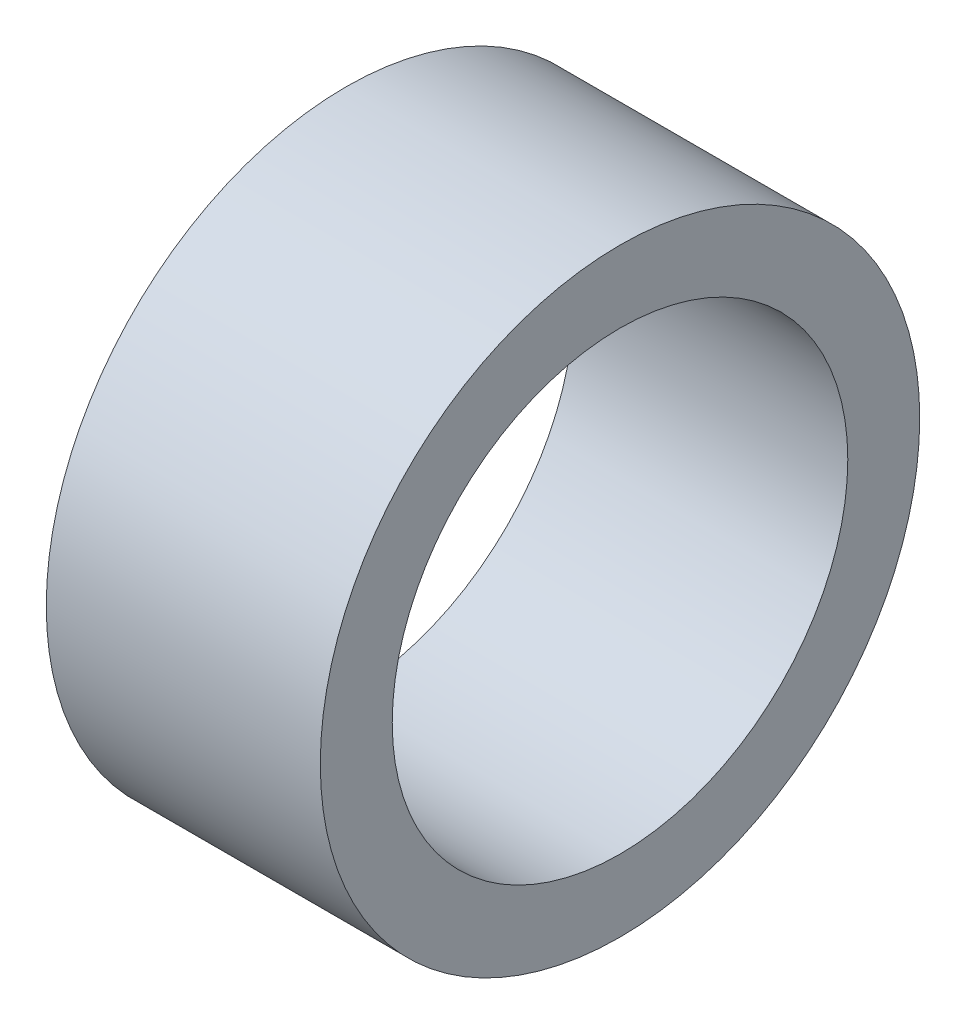
SolidWorks part; units mm, degrees
material "Nylon 6/10"
ref_plane "Front Plane" through (0, 0, 0) normal (0, 0, 1) x (1, 0, 0)
ref_plane "Top Plane" through (0, 0, 0) normal (0, 1, 0) x (1, 0, 0)
ref_plane "Right Plane" through (0, 0, 0) normal (1, 0, 0) x (0, 0, -1)
sketch "Sketch1" plane through (0, 0, 0) normal (0, 0, 1) x (1, 0, 0)
  line L0 (31.75, -13.8602) -> (31.75, 12.314) construction
  line L1 (31.75, 5.5563) -> (36.83, 5.5563)
  line L2 (31.75, 5.5563) -> (31.75, 4.2227)
  line L3 (31.75, 4.2227) -> (36.83, 4.2227)
  line L4 (36.83, 5.5563) -> (36.83, 4.2227)
  line L5 (0, 0) -> (42.6651, 0) construction
  line L6 (44.1854, 3.9687) -> (-54.7878, 3.9687) construction
  dimension "D1" = 0.254
  dimension "D2" = 11.1125
  dimension "D3" = 5.08
revolve "Revolve1" add sketch "Sketch1" angle 360 about L5
